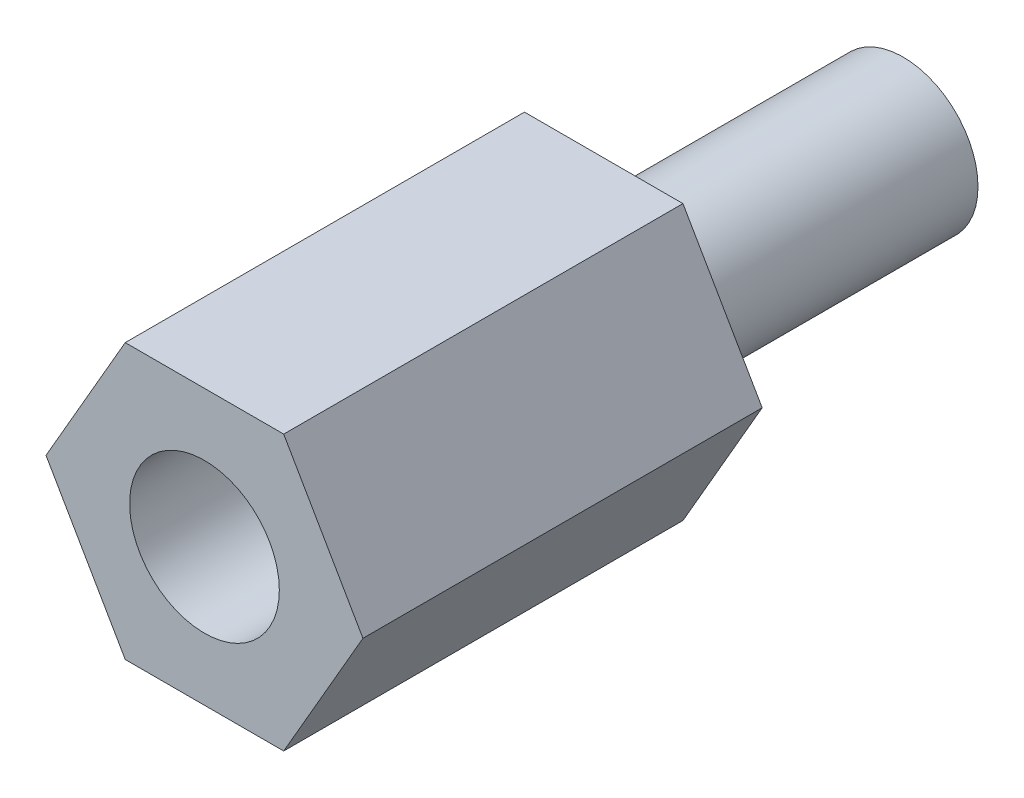
SolidWorks part; units mm, degrees
ref_plane "Front Plane" through (0, 0, 0) normal (0, 0, 1) x (1, 0, 0)
ref_plane "Top Plane" through (0, 0, 0) normal (0, 1, 0) x (1, 0, 0)
ref_plane "Right Plane" through (0, 0, 0) normal (1, 0, 0) x (0, 0, -1)
sketch "Sketch1" plane through (0, 0, 0) normal (0, 0, 1) x (1, 0, 0)
  line L1 (1.5877, -2.75) -> (3.1754, 0)
  line L2 (3.1754, 0) -> (1.5877, 2.75)
  line L3 (1.5877, 2.75) -> (-1.5877, 2.75)
  line L4 (-1.5877, 2.75) -> (-3.1754, 0)
  line L5 (-3.1754, 0) -> (-1.5877, -2.75)
  line L6 (-1.5877, -2.75) -> (1.5877, -2.75)
  circle A0 centre (0, 0) radius 1.5
  circle A1 centre (0, 0) radius 2.75 construction
  dimension "D1" = 5.5
  dimension "D2" = 3
extrude "Boss-Extrude1" add sketch "Sketch1" along normal blind 8 contours L3 L4 L5 L6 L1 L2
extrude "Boss-Extrude2" add sketch "Sketch1<3>" against normal blind 6 contours A0
sketch "Sketch1<3>" plane through (0, 0, 0) normal (0, 0, 1) x (1, 0, 0) same geometry as "Sketch1"
extrude "Cut-Extrude1" cut sketch "Sketch1<4>" against normal blind 6 from surface contours A0 starting at face at (0, 0, 8)
sketch "Sketch1<4>" plane through (0, 0, 0) normal (0, 0, 1) x (1, 0, 0) same geometry as "Sketch1"
